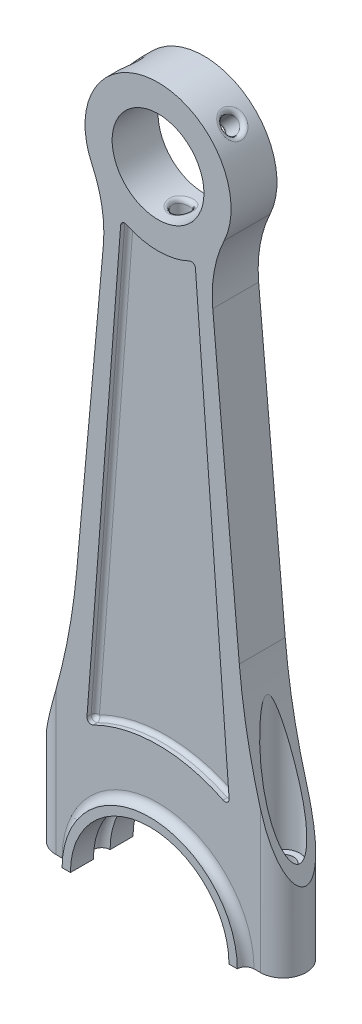
SolidWorks part; units mm, degrees
ref_plane "Front Plane" through (0, 0, 0) normal (0, 0, 1) x (1, 0, 0)
ref_plane "Top Plane" through (0, 0, 0) normal (0, 1, 0) x (1, 0, 0)
ref_plane "Right Plane" through (0, 0, 0) normal (1, 0, 0) x (0, 0, -1)
sketch "Sketch1" plane through (0, 0, 0) normal (0, 0, 1) x (1, 0, 0)
  line L0 (-71.0613, 0) -> (64.1526, 0) construction
  line L1 (0, 0) -> (0, 55.2699) construction
  line L2 (30, 0) -> (30, 18)
  line L3 (-30, 0) -> (-30, 18)
  line L4 (30, 0) -> (19, 0)
  line L5 (-30, 0) -> (-19, 0)
  line L6 (13.1101, 132.1008) -> (19.4763, 61.5215)
  line L7 (-13.1101, 132.1008) -> (-19.4763, 61.5215)
  arc A0 (19, 0) -> (-19, 0) centre (0, 0) ccw
  arc A1 (34.9857, 0) -> (-34.9857, 0) centre (0, 0) ccw construction
  circle A2 centre (0, 155) radius 11
  arc A3 (15.838, 147.5563) -> (-15.838, 147.5563) centre (0, 155) ccw
  arc A4 (13.1101, 132.1008) -> (15.838, 147.5563) centre (42.9888, 134.7958) cw
  arc A5 (19.4763, 61.5215) -> (30, 18) centre (171.404, 75.2252) ccw
  arc A6 (-19.4763, 61.5215) -> (-30, 18) centre (-171.404, 75.2252) cw
  arc A7 (-13.1101, 132.1008) -> (-15.838, 147.5563) centre (-42.9888, 134.7958) ccw
  dimension "D1" = 38
  dimension "D4" = 22
  dimension "D6" = 35
  dimension "D7" = 30
  dimension "D2" = 18
  dimension "D3" = 60
  dimension "D5" = 155
extrude "Boss-Extrude1" add sketch "Sketch1" along normal blind 11
sketch "Sketch2" plane through (0, 0, 11) normal (0, 0, 1) x (1, 0, 0)
  line L0 (8.8478, 139.9014) -> (17.1738, 30.4969)
  line L1 (0, 0) -> (0, 155) construction
  line L2 (-8.8478, 139.9014) -> (-17.1738, 30.4969)
  arc A0 (-8.8478, 139.9014) -> (8.8478, 139.9014) centre (0, 155) ccw
  arc A1 (17.1738, 30.4969) -> (-17.1738, 30.4969) centre (0, 0) ccw
  dimension "D1" = 35
  dimension "D2" = 70
extrude "Cut-Extrude1" cut sketch "Sketch2" against normal blind 2
sketch "Sketch3" plane through (0, 0, 0) normal (0, -1, 0) x (1, 0, 0)
  line L0 (19, 11) -> (30, 0) construction
  line L1 (0, 0) -> (0, 23.352) construction
  line L2 (-19, 0) -> (19, 0) construction
  circle A0 centre (24.5, 5.5) radius 2.5
  circle A1 centre (-24.5, 5.5) radius 2.5
  dimension "D1" = 5
extrude "Cut-Extrude2" cut sketch "Sketch3" against normal through all
sketch "Sketch4" plane through (0, 0, 0) normal (0, -1, 0) x (1, 0, 0)
  line L0 (0, 0) -> (0, 25.0072) construction
  line L1 (-19, 0) -> (19, 0) construction
  circle A0 centre (-24.5, 5.5) radius 4
  circle A1 centre (24.5, 5.5) radius 4
  dimension "D1" = 8
extrude "Cut-Extrude3" cut sketch "Sketch4" against normal through all from offset 20 offset against normal yes
sketch "Sketch5" plane through (0, 0, 11) normal (0, 0, 1) x (1, 0, 0)
  line L0 (-19, 0) -> (-21, 0)
  line L1 (21, 0) -> (19, 0)
  line L8 (19, 0) -> (30, 0)
  line L9 (30, 0) -> (30, 18)
  line L10 (19.4763, 61.5215) -> (13.1101, 132.1008)
  line L11 (-13.1101, 132.1008) -> (-19.4763, 61.5215)
  line L12 (-30, 18) -> (-30, 0)
  line L13 (-30, 0) -> (-19, 0)
  arc A0 (21, 0) -> (-21, 0) centre (0, 0) ccw
  arc A7 (19.4763, 61.5215) -> (30, 18) centre (171.404, 75.2252) ccw
  arc A8 (15.838, 147.5563) -> (13.1101, 132.1008) centre (42.9888, 134.7958) ccw
  arc A9 (15.838, 147.5563) -> (-15.838, 147.5563) centre (0, 155) ccw
  arc A10 (-13.1101, 132.1008) -> (-15.838, 147.5563) centre (-42.9888, 134.7958) ccw
  arc A11 (-30, 18) -> (-19.4763, 61.5215) centre (-171.404, 75.2252) ccw
  arc A12 (19, 0) -> (-19, 0) centre (0, 0) ccw
  arc A18 (19, 0) -> (-19, 0) centre (0, 0) ccw
  dimension "D1" = 42
  dimension "D2" = 0
extrude "Boss-Extrude2" add sketch "Sketch5" along normal blind 2
sketch "Sketch6" plane through (-30, 0, 0) normal (-1, 0, 0) x (0, 0, 1)
  line L0 (5.5, 0) -> (5.5, 18) construction
  line L1 (11, 0) -> (0, 0) construction
  line L2 (11, 18) -> (0, 18) construction
ref_plane "Plane2" through (0, 0, 5.5) normal (0, 0, 1) x (1, 0, 0)
mirror "Mirror3" about plane through (0, 0, 5.5) normal (0, 0, 1) of "Cut-Extrude1", "Boss-Extrude2"
fillet "Fillet1" radius 2 2 edges at (0, 21, 11) (0, 21, 0)
sketch "Sketch7" plane through (0, 0, 0) normal (0, -1, 0) x (1, 0, 0)
  line L0 (19, 13) -> (19, -2) construction
  line L1 (0, 0) -> (0, 24.7707) construction
  circle A0 centre (19, 5.5) radius 2
  dimension "D1" = 4
revolve "Cut-Revolve1" cut sketch "Sketch7" angle 360 about L1
sketch "Sketch8" plane through (0, 0, 0) normal (0, -1, 0) x (1, 0, 0)
  line L0 (30, 11) -> (30, 0) construction
  circle A0 centre (0, 5.5) radius 2
  point P7 (30, 5.5)
  dimension "D1" = 4
extrude "Cut-Extrude4" cut sketch "Sketch8" against normal up to next
sketch "Sketch10" plane through (0, 0, 5.5) normal (0, 0, 1) x (1, 0, 0)
  line L0 (0, 155) -> (0, 172.5) construction
  line L1 (0, 155) -> (-14.1423, 169.1423) construction
  line L2 (-13.1898, 168.1898) -> (-6.3743, 161.3743)
  line L3 (-13.1898, 168.1898) -> (-11.7756, 169.604)
  line L4 (-6.3743, 161.3743) -> (-4.9601, 162.7886)
  line L5 (-11.7756, 169.604) -> (-4.9601, 162.7886)
  arc A0 (15.838, 147.5563) -> (-15.838, 147.5563) centre (0, 155) ccw construction
  dimension "D1" = 45
  dimension "D2" = 2
revolve "Cut-Revolve2" cut sketch "Sketch10" angle 360 about L2
mirror "Mirror4" about plane through (0, 0, 0) normal (1, 0, 0) of "Cut-Revolve2"
fillet "Fillet2" radius 1 5 edges at (10.9186, 168.676, 5.9454) (6.2722, 164.0366, 5.9233) (-10.9186, 168.676, 5.0546) (-6.2722, 164.0366, 5.0767) (-0.4232, 144.0081, 7.4547)
fillet "Fillet3" radius 1 16 edges at (-8.8478, 139.9014, 1) (8.8478, 139.9014, 1) (-17.1738, 30.4969, 1) (17.1738, 30.4969, 1) (-17.1738, 30.4969, 10) (17.1738, 30.4969, 10) (-8.8478, 139.9014, 10) (8.8478, 139.9014, 10) (-13.0108, 85.1992, 9) (0, 137.5, 9) (13.0108, 85.1992, 9) (0, 35, 9) (13.0108, 85.1992, 2) (0, 137.5, 2) (-13.0108, 85.1992, 2) (0, 35, 2)
fillet "Fillet4" 2 edges at (30, 9, 11) (30, 9, 0) type full round first side face at (0, 63.824, 11) second side face at (11, 155, 0) middle face at (30, 9, 5.5)
fillet "Fillet5" 2 edges at (-30, 9, 11) (-30, 9, 0) type full round first side face at (-0.8351, 65.1907, 11) second side face at (11, 155, 0) middle face at (-30, 9, 5.5)
